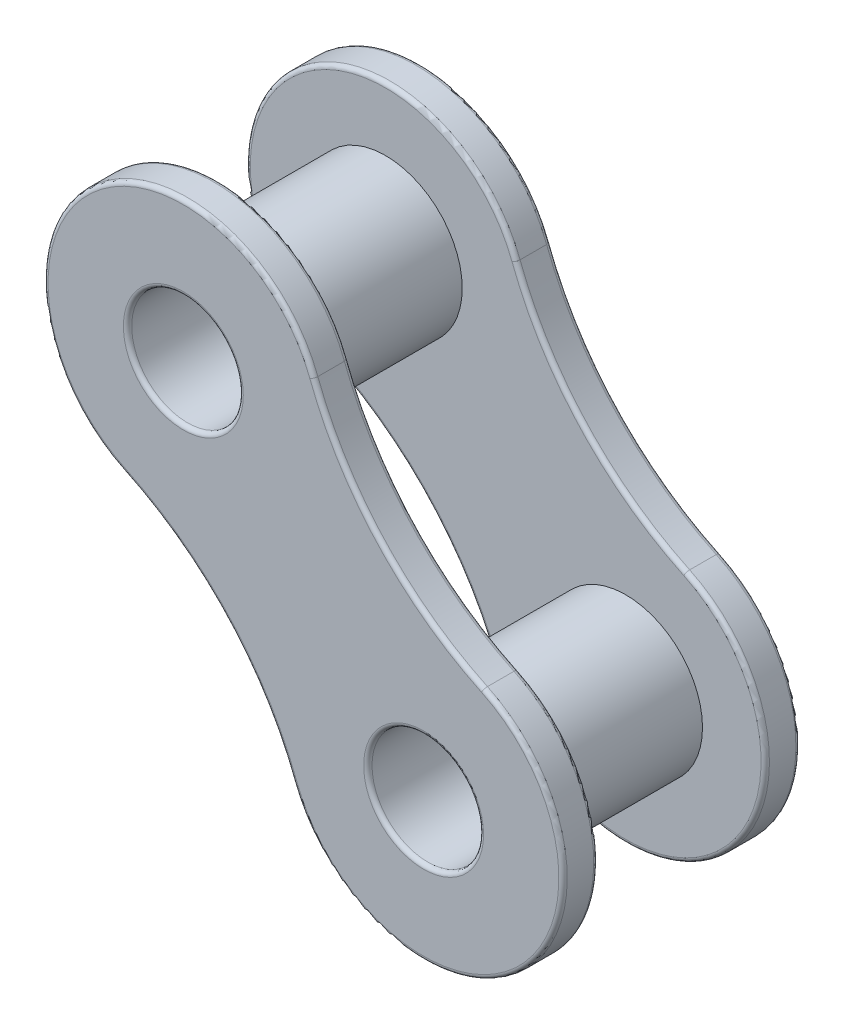
SolidWorks part; units mm, degrees
material "AISI 1035 Steel (SS)"
ref_plane "Front Plane" through (0, 0, 0) normal (0, 0, 1) x (1, 0, 0)
ref_plane "Top Plane" through (0, 0, 0) normal (0, 1, 0) x (1, 0, 0)
ref_plane "Right Plane" through (0, 0, 0) normal (1, 0, 0) x (0, 0, -1)
sketch "Sketch1" plane through (0, 0, 0) normal (0, 0, 1) x (1, 0, 0)
  line L0 (0, 0) -> (175.9404, -55.6384)
  line L1 (0, -154.3346) -> (175.9404, -98.6962)
  line L2 (55.9641, -86.7293) -> (56.4705, -74.0394)
  line L3 (15.0998, -147.806) -> (25.6638, -140.7567)
  line L4 (25.6638, -140.7567) -> (34.995, -132.1417)
  line L5 (34.995, -132.1417) -> (42.8636, -122.173)
  line L6 (42.8636, -122.173) -> (49.0759, -111.0961)
  line L7 (49.0759, -111.0961) -> (53.4789, -99.1837)
  line L8 (53.4789, -99.1837) -> (55.9641, -86.7293)
  line L9 (56.4705, -74.0394) -> (54.9855, -61.4265)
  line L10 (54.9855, -61.4265) -> (51.5457, -49.2012)
  line L11 (51.5457, -49.2012) -> (46.2358, -37.6645)
  line L12 (46.2358, -37.6645) -> (39.1865, -27.1005)
  line L13 (39.1865, -27.1005) -> (30.5714, -17.7694)
  line L14 (30.5714, -17.7694) -> (20.6027, -9.9008)
  line L15 (20.6027, -9.9008) -> (9.5258, -3.6885)
  line L16 (9.5258, -3.6885) -> (-2.3865, 0.7145)
  line L17 (-2.3865, 0.7145) -> (-14.841, 3.1998)
  line L18 (-14.841, 3.1998) -> (-27.5309, 3.7061)
  line L19 (-27.5309, 3.7061) -> (-40.1437, 2.2211)
  line L20 (-40.1437, 2.2211) -> (-52.369, -1.2187)
  line L21 (-52.369, -1.2187) -> (-63.9057, -6.5286)
  line L22 (-63.9057, -6.5286) -> (-74.4697, -13.5779)
  line L23 (-74.4697, -13.5779) -> (-83.8009, -22.1929)
  line L24 (-83.8009, -22.1929) -> (-91.6695, -32.1616)
  line L25 (-91.6695, -32.1616) -> (-97.8817, -43.2385)
  line L26 (-97.8817, -43.2385) -> (-102.2847, -55.1509)
  line L27 (-102.2847, -55.1509) -> (-104.77, -67.6053)
  line L28 (-104.77, -67.6053) -> (-105.2764, -80.2952)
  line L29 (-105.2764, -80.2952) -> (-103.7914, -92.9081)
  line L30 (-103.7914, -92.9081) -> (-100.3515, -105.1334)
  line L31 (-100.3515, -105.1334) -> (-95.0416, -116.6701)
  line L32 (-95.0416, -116.6701) -> (-87.9924, -127.2341)
  line L33 (-87.9924, -127.2341) -> (-79.3773, -136.5652)
  line L34 (-79.3773, -136.5652) -> (-69.4086, -144.4338)
  line L35 (-69.4086, -144.4338) -> (-58.3317, -150.6461)
  line L36 (-58.3317, -150.6461) -> (-46.4194, -155.0491)
  line L37 (-46.4194, -155.0491) -> (-33.9649, -157.5344)
  line L38 (-33.9649, -157.5344) -> (-21.275, -158.0407)
  line L39 (-21.275, -158.0407) -> (-8.6621, -156.5557)
  line L40 (-8.6621, -156.5557) -> (3.5632, -153.1159)
  line L41 (3.5632, -153.1159) -> (15.0998, -147.806)
  line L43 (170.9991, -99.6698) -> (182.8685, -95.0883)
  line L44 (182.8685, -95.0883) -> (190.3767, -84.8171)
  line L45 (190.3767, -84.8171) -> (191.14, -72.1171)
  line L46 (191.14, -72.1171) -> (184.916, -61.0205)
  line L47 (184.916, -61.0205) -> (173.6808, -55.0504)
  line L48 (173.6808, -55.0504) -> (161.0014, -56.1023)
  line L49 (161.0014, -56.1023) -> (150.9035, -63.8421)
  line L50 (150.9035, -63.8421) -> (146.5932, -75.8127)
  line L51 (146.5932, -75.8127) -> (149.4388, -88.2133)
  line L52 (149.4388, -88.2133) -> (158.537, -97.1069)
  line L53 (158.537, -97.1069) -> (170.9991, -99.6698)
  arc A0 (0, 0) -> (0, -154.3346) centre (-24.4029, -77.1673) ccw
  arc A1 (175.9404, -98.6962) -> (175.9404, -55.6384) centre (169.1323, -77.1673) ccw
  circle A2 centre (-24.4029, -77.1673) radius 80.6844 construction
  circle A3 centre (169.1323, -77.1673) radius 21.6651 construction
  dimension "D1" = 730
  dimension "D2" = 12.7
  dimension "D3" = 12.7
sketch "Sketch2" plane through (0, 0, 0) normal (0, 0, 1) x (1, 0, 0)
  line L0 (0, -154.3346) -> (175.9404, -98.6962) construction
  line L1 (0, 0) -> (175.9404, -55.6384) construction
  line L2 (0, -154.3346) -> (175.9404, -98.6962)
  line L3 (0, 0) -> (175.9404, -55.6384)
  arc A0 (175.9404, -98.6962) -> (175.9404, -55.6384) centre (169.1323, -77.1673) ccw construction
  arc A1 (0, 0) -> (0, -154.3346) centre (-24.4029, -77.1673) ccw construction
  arc A2 (175.9404, -98.6962) -> (175.9404, -55.6384) centre (169.1323, -77.1673) ccw
  arc A3 (0, 0) -> (0, -154.3346) centre (-24.4029, -77.1673) ccw
sketch "Sketch3" plane through (0, 0, 0) normal (0, 0, 1) x (1, 0, 0)
  circle A0 centre (30.5714, -17.7694) radius 2
  circle A1 centre (39.1865, -27.1005) radius 2
  circle A2 centre (30.5714, -17.7694) radius 5
  circle A3 centre (39.1865, -27.1005) radius 5
  arc A4 (28.4306, -22.2879) -> (34.5118, -28.8746) centre (23.2925, -33.1322) cw
  arc A5 (35.2461, -15.9953) -> (41.3274, -22.5821) centre (46.4654, -11.7377) ccw
  dimension "D1" = 4
  dimension "D2" = 10
  dimension "D3" = 12
sketch "Sketch4" plane through (0, 0, 0) normal (0, 0, 1) x (1, 0, 0)
  circle A0 centre (30.5714, -17.7694) radius 2.75
  circle A1 centre (39.1865, -27.1005) radius 2.75
  circle A2 centre (39.1865, -27.1005) radius 2 construction
  circle A3 centre (30.5714, -17.7694) radius 2 construction
  circle A4 centre (39.1865, -27.1005) radius 2
  circle A5 centre (30.5714, -17.7694) radius 2
  dimension "D1" = 5.5
extrude "Boss-Extrude1" add sketch "Sketch4" along normal blind 3 and the other way blind 3
sketch "Sketch5" plane through (0, 0, 3) normal (0, 0, 1) x (1, 0, 0)
  arc A0 (35.2461, -15.9953) -> (41.3274, -22.5821) centre (46.4654, -11.7377) ccw construction
  circle A1 centre (39.1865, -27.1005) radius 5
  arc A2 (34.5118, -28.8746) -> (41.3274, -22.5821) centre (39.1865, -27.1005) ccw
  circle A3 centre (30.5714, -17.7694) radius 5
  arc A4 (35.2461, -15.9953) -> (28.4306, -22.2879) centre (30.5714, -17.7694) ccw
  circle A5 centre (39.1865, -27.1005) radius 2
  circle A6 centre (39.1865, -27.1005) radius 2
  circle A7 centre (30.5714, -17.7694) radius 2
  circle A8 centre (30.5714, -17.7694) radius 2
  arc A9 (34.5118, -28.8746) -> (28.4306, -22.2879) centre (23.2925, -33.1322) ccw construction
  arc A10 (35.2461, -15.9953) -> (41.3274, -22.5821) centre (46.4654, -11.7377) ccw
  arc A11 (34.5118, -28.8746) -> (28.4306, -22.2879) centre (23.2925, -33.1322) ccw
  dimension "D1" = 0
  dimension "D2" = 0
  dimension "D3" = 0
  dimension "D4" = 0
extrude "Boss-Extrude2" add sketch "Sketch5" along normal blind 1.25
sketch "Sketch8" plane through (0, 0, -3) normal (0, 0, -1) x (-1, 0, 0)
  arc A0 (-41.3274, -22.5821) -> (-35.2461, -15.9953) centre (-46.4654, -11.7377) ccw construction
  circle A1 centre (-39.1865, -27.1005) radius 5
  arc A2 (-41.3274, -22.5821) -> (-34.5118, -28.8746) centre (-39.1865, -27.1005) ccw
  circle A3 centre (-30.5714, -17.7694) radius 5
  arc A4 (-28.4306, -22.2879) -> (-35.2461, -15.9953) centre (-30.5714, -17.7694) ccw
  circle A5 centre (-39.1865, -27.1005) radius 2
  circle A6 centre (-39.1865, -27.1005) radius 2
  circle A7 centre (-30.5714, -17.7694) radius 2
  circle A8 centre (-30.5714, -17.7694) radius 2
  arc A9 (-28.4306, -22.2879) -> (-34.5118, -28.8746) centre (-23.2925, -33.1322) ccw construction
  arc A10 (-41.3274, -22.5821) -> (-35.2461, -15.9953) centre (-46.4654, -11.7377) ccw
  arc A11 (-28.4306, -22.2879) -> (-34.5118, -28.8746) centre (-23.2925, -33.1322) ccw
  dimension "D1" = 0
  dimension "D2" = 0
  dimension "D3" = 0
  dimension "D4" = 0
extrude "Boss-Extrude3" add sketch "Sketch8" along normal blind 1.25
fillet "Fillet5" radius 0.15 20 edges at (27.1797, -14.0957, -4.25) (32.1094, -24.992, -4.25) (42.5782, -30.7742, -4.25) (27.1797, -14.0957, -3) (32.1094, -24.992, -3) (42.5782, -30.7742, -3) (42.5782, -30.7742, 4.25) (32.1094, -24.992, 4.25) (27.1797, -14.0957, 4.25) (42.5782, -30.7742, 3) (32.1094, -24.992, 3) (27.1797, -14.0957, 3) (37.6486, -19.8779, -4.25) (37.6486, -19.8779, -3) (37.6486, -19.8779, 4.25) (37.6486, -19.8779, 3) (37.1865, -27.1005, -4.25) (41.1865, -27.1005, 4.25) (28.5714, -17.7694, -4.25) (32.5714, -17.7694, 4.25)
ref_plane "Midplane" through (0, 0, 0) normal (0, 0, 1) x (1, 0, 0)
sketch "Sketch9" plane through (0, 0, 0) normal (0, 0, 1) x (1, 0, 0)
  circle A0 centre (30.5714, -17.7694) radius 2 construction
  circle A1 centre (30.5714, -17.7694) radius 2
  circle A2 centre (39.1865, -27.1005) radius 2 construction
  circle A3 centre (39.1865, -27.1005) radius 2
